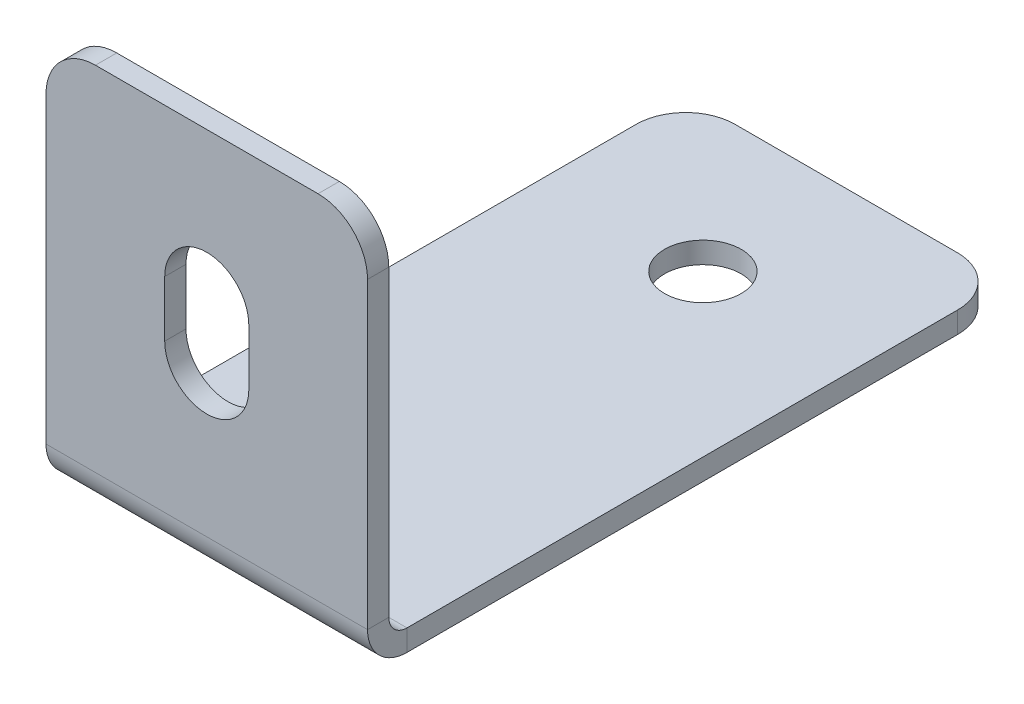
SolidWorks part; units mm, degrees
note: The reader was unsure of these and kept them because the rebuilt part matched: flange length of "Edge-Flange1".
ref_plane "Front Plane" through (0, 0, 0) normal (0, 0, 1) x (1, 0, 0)
ref_plane "Top Plane" through (0, 0, 0) normal (0, 1, 0) x (1, 0, 0)
ref_plane "Right Plane" through (0, 0, 0) normal (1, 0, 0) x (0, 0, -1)
sketch "Sketch1" plane through (0, 0, 0) normal (0, 1, 0) x (1, 0, 0)
  line L1 (-6.5, -12.5) -> (6.5, -12.5)
  line L2 (-6.5, -12.5) -> (-6.5, 12.5)
  line L3 (-6.5, 12.5) -> (6.5, 12.5)
  line L4 (6.5, -12.5) -> (6.5, 12.5)
  line L5 (-6.5, -12.5) -> (6.5, 12.5) construction
  line L6 (-6.5, 12.5) -> (6.5, -12.5) construction
  point P0 (0, 0)
  dimension "D1" = 13
  dimension "D2" = 25
base flange "Base-Flange1" sketch "Sketch1" thickness 0.86 reverse thickness direction no parameters "D1"=0.7366
edge flange "Edge-Flange1" sketch "Sketch9" flange angle 90 flange length 15 flange position material outside bend radius 0.7366 thickness 0.86 relief rectangular parameters "D6"=10
sketch "Sketch9" plane through (0, 0, 12.5) normal (0, 0, 1) x (1, 0, 0)
  line L0 (-6.5, 0) -> (6.5, 0) construction
  line L1 (-6.5, 0) -> (6.5, 0)
  line L2 (-6.5, 0) -> (-6.5, 15)
  line L3 (-6.5, 15) -> (6.5, 15)
  line L4 (6.5, 15) -> (6.5, 0)
bend "EdgeBend1" bend radius 0.7366 bend angle 90 parameters "D5"=1
sketch "Sketch10" plane through (0, 0, 0) normal (0, 1, 0) x (1, 0, 0)
  line L0 (6.5, 12.5) -> (-6.5, 12.5) construction
  circle A0 centre (0, 6.7) radius 1.55
  dimension "D1" = 5.8
sketch "Sketch11" plane through (0, 0, 12.5) normal (0, 0, -1) x (-1, 0, 0)
  line L0 (0, 9) -> (0, 6.7366) construction
  line L1 (1.7, 9) -> (1.7, 6.7366)
  line L2 (-1.7, 9) -> (-1.7, 6.7366)
  line L3 (-6.5, 15) -> (6.5, 15) construction
  line L4 (6.5, 0.7366) -> (-6.5, 0.7366) construction
  arc A0 (1.7, 9) -> (-1.7, 9) centre (0, 9) ccw
  arc A1 (-1.7, 6.7366) -> (1.7, 6.7366) centre (0, 6.7366) ccw
  point P3 (0, 7.8683)
  point P8 (0, 15)
  dimension "D1" = 6
  dimension "D2" = 6
fillet "Fillet1" radius 2 4 edges at (-6.5, 15, 12.93) (6.5, 15, 12.93) (-6.5, -0.43, -12.5) (6.5, -0.43, -12.5)
extrude "Cut-Extrude1" cut sketch "Sketch10" against normal through all contours A0 normal cut yes
extrude "Cut-Extrude2" cut sketch "Sketch11" against normal through all contours A0 L2 A1 L1 normal cut yes
sketch "Bend-Lines1" plane through (0, 0, 0) normal (0, 1, 0) x (1, 0, 0)
sketch "Bounding-Box1" plane through (0, 0, 0) normal (0, 1, 0) x (1, 0, 0)
sheet metal parameters "Sheet-Metal(1)" thickness 0.86 parameters "D1"=0.7366
flat pattern "Flat-Pattern(1)" [suppressed]
sketch "Bend-Lines2" plane through (0, 0, 0) normal (0, 1, 0) x (1, 0, 0)
sketch "Bounding-Box2" [suppressed] plane through (0, 0, 0) normal (0, 1, 0) x (1, 0, 0)
sheet metal parameters "Sheet-Metal(2)" thickness 0.86 parameters "D1"=0.7366
flat pattern "Flat-Pattern(1)" [suppressed]
sketch "Bend-Lines2" plane through (0, 0, 0) normal (0, 1, 0) x (1, 0, 0)
sketch "Bounding-Box2" [suppressed] plane through (0, 0, 0) normal (0, 1, 0) x (1, 0, 0)
bend of the flat pattern "Flatten-<EdgeBend1>1"
sheet metal parameters "Sheet-Metal(3)" thickness 0.86 parameters "D1"=0.7366
flat pattern "Flat-Pattern(1)" [suppressed]
sketch "Bend-Lines2" plane through (0, 0, 0) normal (0, 1, 0) x (1, 0, 0)
sketch "Bounding-Box2" [suppressed] plane through (0, 0, 0) normal (0, 1, 0) x (1, 0, 0)
bend of the flat pattern "Flatten-<EdgeBend1>1"
sheet metal parameters "Sheet-Metal(4)" thickness 0.86 parameters "D1"=0.7366
flat pattern "Flat-Pattern(1)" [suppressed]
sketch "Bend-Lines2" plane through (0, 0, 0) normal (0, 1, 0) x (1, 0, 0)
sketch "Bounding-Box2" [suppressed] plane through (0, 0, 0) normal (0, 1, 0) x (1, 0, 0)
bend of the flat pattern "Flatten-<EdgeBend1>1"
